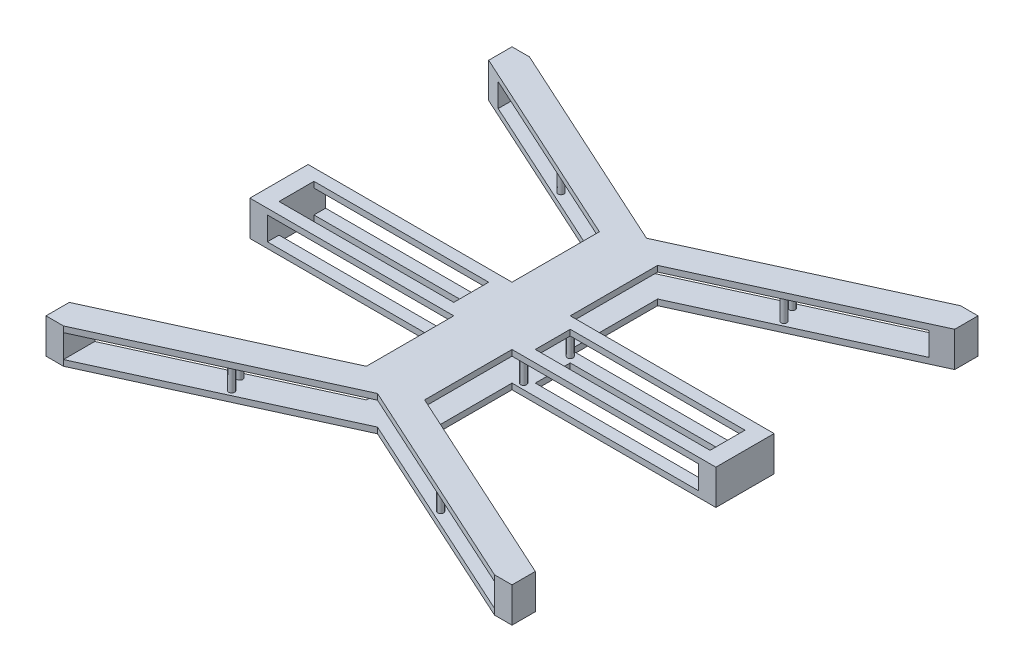
SolidWorks part; units mm, degrees
ref_plane "Front Plane" through (0, 0, 0) normal (0, 0, 1) x (1, 0, 0)
ref_plane "Top Plane" through (0, 0, 0) normal (0, 1, 0) x (1, 0, 0)
ref_plane "Right Plane" through (0, 0, 0) normal (1, 0, 0) x (0, 0, -1)
sketch "Sketch1" plane through (0, 0, 0) normal (0, 1, 0) x (1, 0, 0)
  line L1 (-6.6, 0) -> (6.6, 0) construction
  line L2 (160, 20) -> (160, -20)
  line L3 (160, -20) -> (20, -20)
  line L4 (20, -20) -> (20, -80)
  line L5 (20, -80) -> (160, -144)
  line L6 (160, -144) -> (160, -160)
  line L7 (160, -160) -> (148, -160)
  line L8 (148, -160) -> (0, -92.3429)
  line L9 (0, -6.6) -> (0, 6.6) construction
  line L11 (-160, 20) -> (-160, -20)
  line L12 (-160, -20) -> (-20, -20)
  line L13 (-20, -20) -> (-20, -80)
  line L14 (-20, -80) -> (-160, -144)
  line L15 (-160, -144) -> (-160, -160)
  line L16 (-160, -160) -> (-148, -160)
  line L17 (-148, -160) -> (0, -92.3429)
  line L18 (160, 20) -> (20, 20)
  line L19 (20, 20) -> (20, 80)
  line L20 (160, 160) -> (148, 160)
  line L21 (160, 144) -> (160, 160)
  line L22 (20, 80) -> (160, 144)
  line L23 (148, 160) -> (0, 92.3429)
  line L24 (-160, 144) -> (-160, 160)
  line L25 (-160, 160) -> (-148, 160)
  line L26 (-148, 160) -> (0, 92.3429)
  line L27 (-20, 80) -> (-160, 144)
  line L28 (-160, 20) -> (-20, 20)
  line L29 (-20, 20) -> (-20, 80)
  point P21 (160, 0)
  point P33 (-160, 0)
  dimension "D3" = 20
  dimension "D5" = 16
  dimension "D6" = 60
  dimension "D8" = 12
  dimension "D1" = 160
  dimension "D2" = 160
  dimension "D4" = 160
  dimension "D7" = 20
extrude "Boss-Extrude1" add sketch "Sketch1" along normal blind 12 and the other way blind 12
sketch "Sketch2" plane through (0, 0, 160) normal (0, 0, 1) x (1, 0, 0)
  line L0 (-148, -12) -> (-148, 12) construction
  line L1 (-148, -8) -> (148, -8)
  line L2 (-148, -8) -> (-148, 8)
  line L3 (-148, 8) -> (148, 8)
  line L4 (148, -8) -> (148, 8)
  line L5 (148, -12) -> (148, 12) construction
  line L7 (88, 0) -> (-88, 0) construction
  dimension "D1" = 8
  dimension "D2" = 8
extrude "Cut-Extrude1" cut sketch "Sketch2" against normal blind 320
sketch "Sketch4" plane through (0, 12, 0) normal (0, 1, 0) x (1, 0, 0)
  line L0 (-6.6, 0) -> (6.6, 0) construction
  line L1 (-148, 12) -> (-28, 12)
  line L2 (-148, 12) -> (-148, -12)
  line L3 (-148, -12) -> (-28, -12)
  line L4 (-28, 12) -> (-28, -12)
  line L5 (-160, 20) -> (-160, -20) construction
  line L7 (0, -6.6) -> (0, 6.6) construction
  line L8 (148, -12) -> (28, -12)
  line L9 (28, 12) -> (28, -12)
  line L10 (148, 12) -> (28, 12)
  line L11 (148, 12) -> (148, -12)
  dimension "D1" = 12
  dimension "D2" = 12
  dimension "D3" = 12
  dimension "D4" = 120
extrude "Cut-Extrude2" cut sketch "Sketch4" against normal blind 24
sketch "Sketch5" plane through (0, -8, 0) normal (0, 1, 0) x (1, 0, 0)
  line L1 (-20, -80) -> (-148, -138.5143) construction
  line L2 (-148, -160) -> (0, -92.3429) construction
  line L4 (-78.2064, -106.6086) -> (-70.0821, -124.3804) construction
  line L5 (0, -6.6) -> (0, 6.6) construction
  line L6 (-28, 12) -> (-28, -12) construction
  line L7 (-28, -12) -> (-148, -12) construction
  line L8 (-6.6, 0) -> (6.6, 0) construction
  circle A0 centre (-71.7452, -120.7425) radius 2
  circle A1 centre (-76.5433, -110.2465) radius 2
  circle A3 centre (-24, -16) radius 2
  circle A4 centre (0, -80.3429) radius 2
  circle A5 centre (24, -16) radius 2
  circle A6 centre (71.7452, -120.7425) radius 2
  circle A7 centre (76.5433, -110.2465) radius 2
  circle A8 centre (76.5433, 110.2465) radius 2
  circle A9 centre (71.7452, 120.7425) radius 2
  circle A10 centre (-71.7452, 120.7425) radius 2
  circle A11 centre (-76.5433, 110.2465) radius 2
  circle A12 centre (0, 80.3429) radius 2
  circle A13 centre (24, 16) radius 2
  circle A14 centre (-24, 16) radius 2
  dimension "D1" = 4
  dimension "D2" = 4
  dimension "D4" = 4
  dimension "D3" = 4
  dimension "D6" = 4
  dimension "D8" = 64
  dimension "D5" = 4
  dimension "D7" = 90
  dimension "D9" = 12
  dimension "D10" = 4
  dimension "D11" = 4
extrude "Boss-Extrude2" add sketch "Sketch5" along normal blind 16
equation "\"A\"= 4"
equation "\"D5@Sketch1\"=4*\"A\""
equation "\"D6@Sketch1\"=15*\"A\""
equation "\"D8@Sketch1\"=3*\"A\""
equation "\"D1@Sketch1\"=40*\"A\""
equation "\"D2@Sketch1\"=40*\"A\""
equation "\"D4@Sketch1\"=40*\"A\""
equation "\"D7@Sketch1\"=5*\"A\""
equation "\"D1@Boss-Extrude1\"=3*\"A\""
equation "\"D2@Boss-Extrude1\"=3*\"A\""
equation "\"D1@Sketch2\"=2*\"A\""
equation "\"D2@Sketch2\"=2*\"A\""
equation "\"D1@Sketch4\"=3*\"A\""
equation "\"D2@Sketch4\"=3*\"A\""
equation "\"D3@Sketch4\"=3*\"A\""
equation "\"D4@Sketch4\"=30*\"A\""
equation "\"D1@Cut-Extrude2\"=6*\"A\""
equation "\"D1@Cut-Extrude1\"=80*\"A\""
equation "\"D3@Sketch1\"=5*\"A\""
equation "\"D1@Sketch5\"=\"A\""
equation "\"D2@Sketch5\"=\"A\""
equation "\"D4@Sketch5\"=\"A\""
equation "\"D6@Sketch5\"=\"A\""
equation "\"D8@Sketch5\"=16*\"A\""
equation "\"D5@Sketch5\"=\"A\""
equation "\"D3@Sketch5\"=\"A\""
equation "\"D9@Sketch5\"=3*\"A\""
equation "\"D10@Sketch5\"=\"A\""
equation "\"D11@Sketch5\"=\"A\""
equation "\"D1@Boss-Extrude2\"=4*\"A\""
